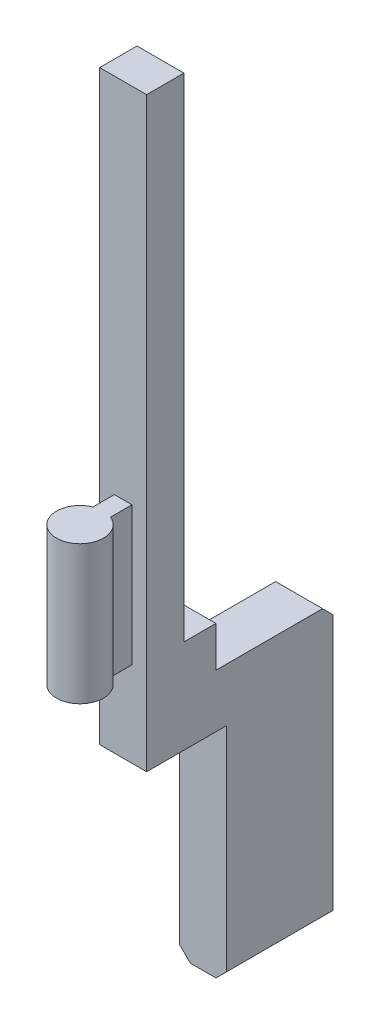
SolidWorks part; units mm, degrees
ref_plane "Płaszczyzna przednia" through (0, 0, 0) normal (0, 0, 1) x (1, 0, 0)
ref_plane "Płaszczyzna górna" through (0, 0, 0) normal (0, 1, 0) x (1, 0, 0)
ref_plane "Płaszczyzna prawa" through (0, 0, 0) normal (1, 0, 0) x (0, 0, -1)
sketch "Szkic1" plane through (0, 0, 0) normal (0, 0, 1) x (1, 0, 0)
  line L1 (-2.2, 10.5) -> (2.2, 10.5)
  line L2 (-2.2, 10.5) -> (-2.2, -10.5)
  line L3 (-2.2, -10.5) -> (2.2, -10.5)
  line L4 (2.2, 10.5) -> (2.2, -10.5)
  line L5 (-2.2, 10.5) -> (2.2, -10.5) construction
  line L6 (-2.2, -10.5) -> (2.2, 10.5) construction
  point P0 (0, 0)
  dimension "D1" = 4.4
  dimension "D2" = 21
extrude "Dodanie-wyciągnięcie1" add sketch "Szkic1" along normal blind 6.5
sketch "Szkic3" plane through (0, 10.5, 0) normal (0, 1, 0) x (1, 0, 0)
  line L0 (0, -6.5) -> (0, -10.55) construction
  line L1 (2.2, -6.5) -> (-2.2, -6.5) construction
  line L3 (0.825, -6.5) -> (0.825, -10.55)
  line L4 (0.825, -6.5) -> (-0.825, -6.5)
  line L5 (-0.825, -6.5) -> (-0.825, -10.55)
  line L6 (0.825, -10.55) -> (-0.825, -10.55)
  line L7 (0.825, -6.5) -> (-0.825, -10.55) construction
  line L8 (-0.825, -6.5) -> (0.825, -10.55) construction
  circle A0 centre (0, -10.55) radius 2.2
  point P5 (0, -8.525)
  line M10 (-2.2, 0) -> (-2.2, -6.5)
  dimension "D2" = 4.4
  dimension "D1" = 4.05
  dimension "D3" = 1.65
extrude "Dodanie-wyciągnięcie2" add sketch "Szkic3" against normal blind 13 contours L5 A0 L3 L6 | L3 A0 L5 L6 | A0 L3 L5 M10 region at (0, 10.5, 7.4519) region at (0, 10.5, 10.8763) region at (0, 10.5, 9.4758)
sketch "Sketch1" plane through (0, 0, 0) normal (0, 0, -1) x (-1, 0, 0)
  line L0 (-2.2, -10.5) -> (-2.2, 10.5) construction
  line L1 (-2.2, -5.5) -> (2.2, -5.5)
  line L2 (-2.2, -5.5) -> (-2.2, -10.5)
  line L3 (-2.2, -10.5) -> (2.2, -10.5)
  line L4 (2.2, -5.5) -> (2.2, -10.5)
  line L5 (0, -10.5) -> (0, -5.5) construction
  line L6 (-2.2, -8) -> (2.2, -8) construction
  line L7 (2.2, 10.5) -> (2.2, -10.5) construction
  line L9 (2.2, -10.5) -> (-2.2, -10.5) construction
  point P460 (0, -8)
  dimension "D1" = 5
extrude "Boss-Extrude1" add sketch "Sketch1" along normal blind 11
sketch "Sketch3" plane through (0, -10.5, 0) normal (0, -1, 0) x (1, 0, 0)
  line L0 (2.2, -11) -> (-2.2, -11) construction
  line L1 (2.2, -11) -> (-2.2, -11)
  line L2 (2.2, -11) -> (2.2, -1)
  line L3 (2.2, -1) -> (-2.2, -1)
  line L4 (-2.2, -11) -> (-2.2, -1)
  line L5 (0, -1) -> (0, -11) construction
  line L6 (2.2, -6) -> (-2.2, -6) construction
  line L7 (2.2, 6.5) -> (2.2, -11) construction
  line L8 (-2.2, 6.5) -> (-2.2, -11) construction
  point P448 (0, -6)
  dimension "D2" = 10
extrude "Boss-Extrude3" add sketch "Sketch3" along normal blind 21
chamfer "Chamfer1" distance 1 angle 45 3 edges at (2.2, -31.5, -6) (-2.2, -31.5, -6) (0, -5.5, -11)
sketch "Sketch5" plane through (0, 10.5, 0) normal (0, 1, 0) x (1, 0, 0)
  line L0 (2.2, -6.5) -> (2.2, 0) construction
  line L1 (-2.2, 0) -> (2.2, 0)
  line L2 (-2.2, 0) -> (-2.2, -3)
  line L3 (-2.2, -3) -> (2.2, -3)
  line L4 (2.2, 0) -> (2.2, -3)
  line L5 (0, -3) -> (0, 0) construction
  line L6 (-2.2, -1.5) -> (2.2, -1.5) construction
  point P212 (0, -1.5)
  dimension "D1" = 3
extrude "Cut-Extrude1" cut sketch "Sketch5" against normal blind 12.2
sketch "Szkic4" plane through (0, 10.5, 0) normal (0, 1, 0) x (1, 0, 0)
  line L0 (-2.2, -6.5) -> (-2.2, -3) construction
  line L1 (-2.2, -3) -> (2.2, -3)
  line L2 (-2.2, -3) -> (-2.2, -6.5)
  line L3 (-2.2, -6.5) -> (2.2, -6.5)
  line L4 (2.2, -3) -> (2.2, -6.5)
  line L5 (-2.2, -3) -> (2.2, -3) construction
  line L6 (2.2, -6.5) -> (2.2, -3) construction
extrude "Dodanie-wyciągnięcie3" add sketch "Szkic4" along normal blind 34
